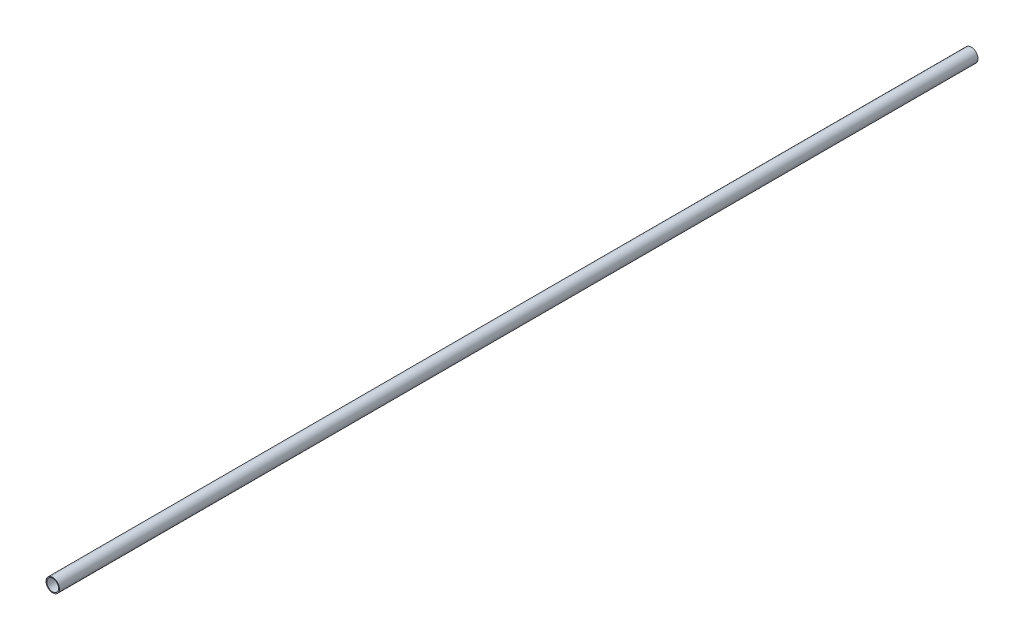
SolidWorks part; units mm, degrees
material "McMaster Carbon Fiber Twill Tube"
ref_plane "Front Plane" through (0, 0, 0) normal (0, 0, 1) x (1, 0, 0)
ref_plane "Top Plane" through (0, 0, 0) normal (0, 1, 0) x (1, 0, 0)
ref_plane "Right Plane" through (0, 0, 0) normal (1, 0, 0) x (0, 0, -1)
sketch "Sketch1" plane through (0, 0, 0) normal (0, 0, 1) x (1, 0, 0)
  circle A0 centre (0, 0) radius 10.922 construction
  circle A1 centre (0, 0) radius 9.525 construction
  point P4 (9.525, 0)
  point P5 (10.922, 0)
  dimension "OD" = 21.844
  dimension "ID" = 19.05
  dimension "Wall Thickness" = 1.397
sketch "Sketch2" plane through (0, 0, 0) normal (1, 0, 0) x (0, 0, -1)
  line L0 (-742.95, 0) -> (742.95, 0) construction
  line L1 (-742.95, -10.922) -> (-742.95, 10.922) construction
  line L2 (-742.95, 10.922) -> (742.95, 10.922) construction
  line L3 (742.95, -10.922) -> (742.95, 10.922) construction
  line L5 (-742.95, -10.922) -> (742.95, -10.922) construction
  point P0 (-721.106, 0)
  point P3 (0, 0)
  point P7 (0, 10.922)
  point P8 (721.106, 0)
  point P11 (-742.95, 0)
  point P13 (742.95, 0)
  dimension "Length" = 1485.9
  dimension "D1" = 21.844
  dimension "D2" = 21.844
sketch "Sketch3" plane through (0, 0, 0) normal (0, 0, 1) x (1, 0, 0)
  circle A0 centre (0, 0) radius 9.525 construction
  circle A1 centre (0, 0) radius 10.922 construction
  circle A2 centre (0, 0) radius 9.525
  circle A3 centre (0, 0) radius 10.922
extrude "Boss-Extrude1" add sketch "Sketch3" along normal up to vertex (742.95 mm away) and the other way up to vertex (742.95 mm away) up to point (0, 0, 742.95) other way up to point (0, 0, -742.95)
equation "\"D1@Sketch2\"=\"OD@Sketch1\""
equation "\"D2@Sketch2\"=\"D1@Sketch2\""
